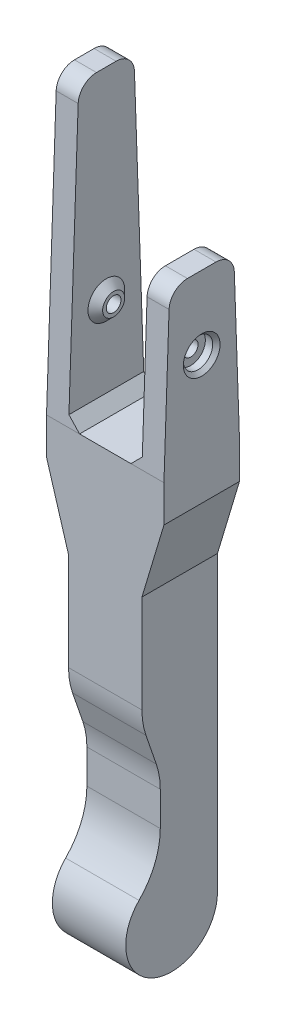
SolidWorks part; units mm, degrees
ref_plane "Front Plane" through (0, 0, 0) normal (0, 0, 1) x (1, 0, 0)
ref_plane "Top Plane" through (0, 0, 0) normal (0, 1, 0) x (1, 0, 0)
ref_plane "Right Plane" through (0, 0, 0) normal (1, 0, 0) x (0, 0, -1)
sketch "Sketch1" plane through (0, 0, 0) normal (1, 0, 0) x (0, 0, -1)
  line L0 (-10.2937, -25) -> (-7.5, 55)
  line L1 (-7.5, 55) -> (7.5, 55)
  line L2 (7.5, 55) -> (10.2937, -25)
  line L3 (10.2937, -25) -> (-10.2937, -25)
  circle A0 centre (0, 0) radius 2
  point P5 (0, -25)
  point P8 (0, 55)
  dimension "D1" = 4
  dimension "D2" = 55
  dimension "D3" = 92
  dimension "D4" = 25
  dimension "D5" = 15
extrude "Boss-Extrude1" add sketch "Sketch1" along normal blind 6
sketch "Sketch2" plane through (0, 0, 0) normal (-1, 0, 0) x (0, 0, 1)
  circle A0 centre (0, 0) radius 4
  dimension "D1" = 8
extrude "Cut-Extrude1" cut sketch "Sketch2" against normal blind 3
sketch "Sketch3" plane through (0, 0, 0) normal (-1, 0, 0) x (0, 0, 1)
  line L1 (-10.2937, -25) -> (10.2937, -25)
  line L2 (-10.2937, -25) -> (-10.2937, -35)
  line L3 (-10.2937, -35) -> (10.2937, -35)
  line L4 (10.2937, -25) -> (10.2937, -35)
  dimension "D1" = 10
extrude "Boss-Extrude2" add sketch "Sketch3" against normal blind 32
sketch "Sketch4" plane through (32, 0, 0) normal (1, 0, 0) x (0, 0, -1)
  line L0 (10.2937, -25) -> (-10.2937, -25)
  line L1 (-10.2937, -25) -> (-8.7222, 20)
  line L2 (-7.5, 55) -> (-10.2937, -25) construction
  line L3 (-8.7222, 20) -> (8.7222, 20)
  line L12 (10.2937, -25) -> (7.5, 55) construction
  line L13 (8.7222, 20) -> (10.2937, -25)
  circle A0 centre (0, 0) radius 2 construction
  circle A1 centre (0, 0) radius 2
  dimension "D1" = 20
extrude "Boss-Extrude3" add sketch "Sketch4" against normal blind 6
fillet "Fillet1" radius 5 4 edges at (3, 55, -7.5) (3, 55, 7.5) (29, 20, -8.7222) (29, 20, 8.7222)
extrude "Cut-Extrude2" cut sketch "Sketch2<2>" along normal blind 3 from surface starting at face at (32, -5.954, 0)
sketch "Sketch2<2>" plane through (0, 0, 0) normal (-1, 0, 0) x (0, 0, 1) same geometry as "Sketch2"
chamfer "Chamfer1" distance 1 angle 45 2 edges at (0, 0, 4) (32, 0, 4)
chamfer "Chamfer2" distance 3 angle 45 2 edges at (6, -25, 0) (26, -25, 0)
sketch "Sketch5" plane through (6, 0, 0) normal (1, 0, 0) x (0, 0, -1)
  circle A0 centre (0, 0) radius 2 construction
  circle A1 centre (0, 0) radius 2
  circle A2 centre (0, 0) radius 3
  dimension "D1" = 1
extrude "Boss-Extrude4" add sketch "Sketch5" along normal blind 2
extrude "Boss-Extrude5" add sketch "Sketch5<2>" against normal blind 2 from surface starting at face at (26, 0, -2)
sketch "Sketch5<2>" plane through (6, 0, 0) normal (1, 0, 0) x (0, 0, -1) same geometry as "Sketch5"
chamfer "Chamfer4" distance 2 angle 45 2 edges at (26, 0, 3) (6, 0, 3)
sketch "Sketch7" plane through (0, 0, -10.2937) normal (0, 0, -1) x (-1, 0, 0)
  line L0 (-32, -35) -> (-26, -55)
  line L1 (-26, -55) -> (-26, -65)
  line L2 (-6, -65) -> (-6, -55)
  line L3 (-6, -55) -> (0, -35)
  line L4 (-6, -65) -> (-26, -65)
  line L5 (-32, -35) -> (0, -35) construction
  line L6 (-16, -65) -> (-16, -35) construction
  line L7 (0, -35) -> (-32, -35)
  dimension "D1" = 20
  dimension "D2" = 10
  dimension "D3" = 20
extrude "Boss-Extrude6" add sketch "Sketch7" against normal up to surface (20.5873 mm away) up to face at (16, -28.3333, 10.2937)
sketch "Sketch8" plane through (26, 0, 0) normal (1, 0, 0) x (0, 0, -1)
  line L1 (10.2937, -65) -> (-10.2937, -65)
  line L2 (-10.2937, -65) -> (-10.2937, -100)
  line L5 (10.2937, -65) -> (10.2937, -135)
  line L6 (-10.2937, -100) -> (-5.2937, -100)
  line L7 (-5.2937, -100) -> (-5.2937, -122.8873)
  arc A2 (-5.2937, -122.8873) -> (10.2937, -135) centre (-2.2063, -135) ccw
  point P10 (10.2937, -100)
  dimension "D1" = 70
  dimension "D2" = 5
  dimension "D3" = 25
extrude "Boss-Extrude7" add sketch "Sketch8" against normal up to surface (20 mm away) up to face at (6, -60, 0)
chamfer "Chamfer5" distance 15 angle 19 1 edges at (16, -100, 10.2937) first distance on face at (16, -48, 10.2937)
fillet "Fillet2" radius 20 3 edges at (16, -122.8873, 5.2937) (16, -99.5211, 5.2937) (16, -85, 10.2937)
